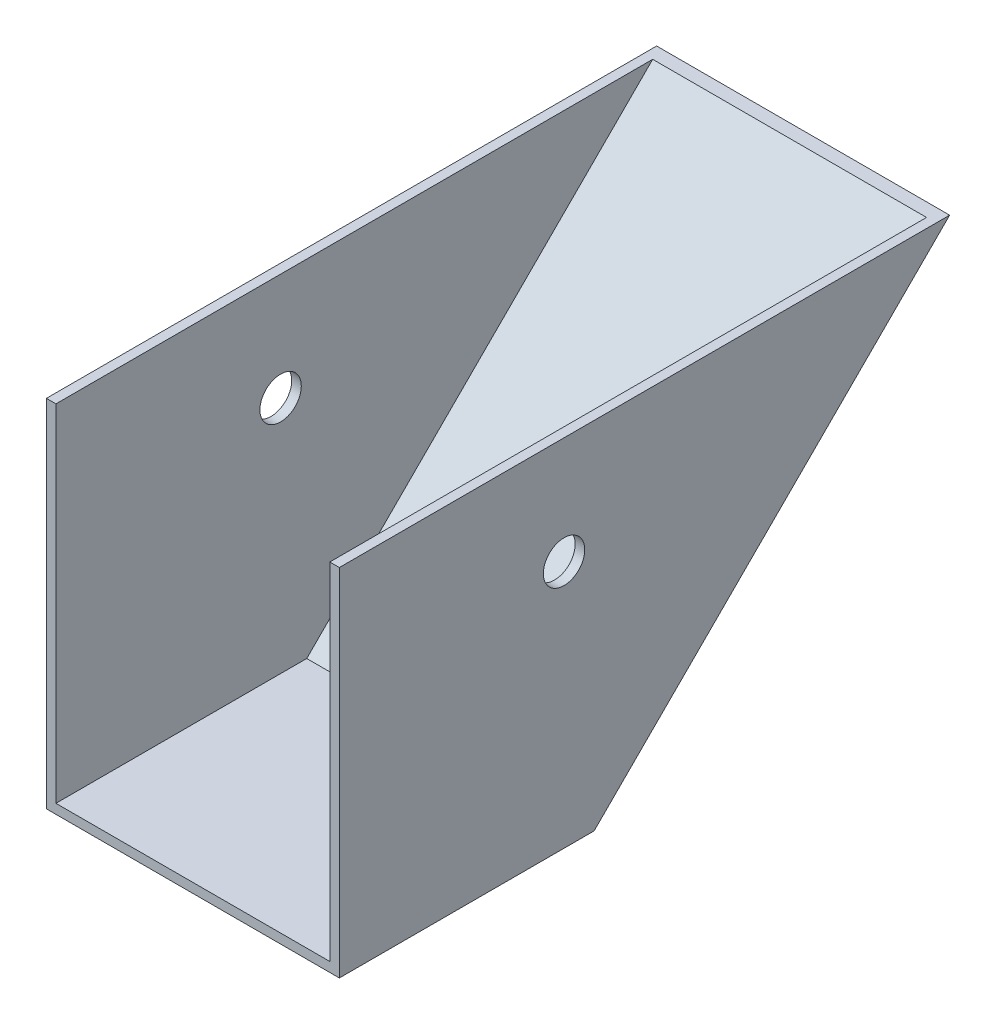
SolidWorks part; units mm, degrees
material "ALUMINUM 6061-T6"
ref_plane "Front Plane" through (0, 0, 0) normal (0, 0, 1) x (1, 0, 0)
ref_plane "Top Plane" through (0, 0, 0) normal (0, 1, 0) x (1, 0, 0)
ref_plane "Right Plane" through (0, 0, 0) normal (1, 0, 0) x (0, 0, -1)
sketch "Sketch2" plane through (0, 0, 0) normal (0, 1, 0) x (1, 0, 0)
  line L1 (-146.05, -317.5) -> (146.05, -317.5)
  line L2 (-146.05, -317.5) -> (-146.05, 317.5)
  line L3 (-146.05, 317.5) -> (146.05, 317.5)
  line L4 (146.05, -317.5) -> (146.05, 317.5)
  line L5 (-146.05, -317.5) -> (146.05, 317.5) construction
  line L6 (-146.05, 317.5) -> (146.05, -317.5) construction
  point P0 (0, 0)
extrude "Boss-Extrude1" add sketch "Sketch2" along normal mid plane 381
sketch "Sketch4" plane through (-146.05, 0, 0) normal (-1, 0, 0) x (0, 0, 1)
  line L0 (-317.5, 190.5) -> (63.5, -190.5)
  line L1 (-317.5, -190.5) -> (317.5, -190.5) construction
  line L2 (-317.5, 190.5) -> (-317.5, -190.5) construction
  line L3 (-317.5, 190.5) -> (-317.5, -190.5)
  line L4 (-317.5, -190.5) -> (63.5, -190.5)
  dimension "D1" = 45
extrude "Cut-Extrude2" cut sketch "Sketch4" against normal blind 381
shell "Shell1" thickness 9.525 removed face at (0, 0, 317.5)
sketch "Sketch5" plane through (0, 190.5, 0) normal (0, 1, 0) x (1, 0, 0)
  line L1 (-146.05, 317.5) -> (146.05, 317.5)
  line L2 (-146.05, 317.5) -> (-146.05, -317.5)
  line L3 (-146.05, -317.5) -> (146.05, -317.5)
  line L4 (146.05, 317.5) -> (146.05, -317.5)
extrude "Cut-Extrude3" cut sketch "Sketch5" against normal blind 24.892
sketch "Sketch6" plane through (-146.05, 0, 0) normal (-1, 0, 0) x (0, 0, 1)
  circle A0 centre (93.5173, 56.9612) radius 20.6375
  dimension "D1" = 41.275
extrude "Cut-Extrude4" cut sketch "Sketch6" against normal blind 514.096
sketch "Sketch10" plane through (0, 165.608, 0) normal (0, 1, 0) x (1, 0, 0)
  line L1 (-146.05, 292.608) -> (146.05, 292.608)
  line L2 (-146.05, 292.608) -> (-146.05, -317.5)
  line L3 (-146.05, -317.5) -> (146.05, -317.5)
  line L4 (146.05, 292.608) -> (146.05, -317.5)
extrude "Cut-Extrude7" cut sketch "Sketch10" against normal blind 1.6933
